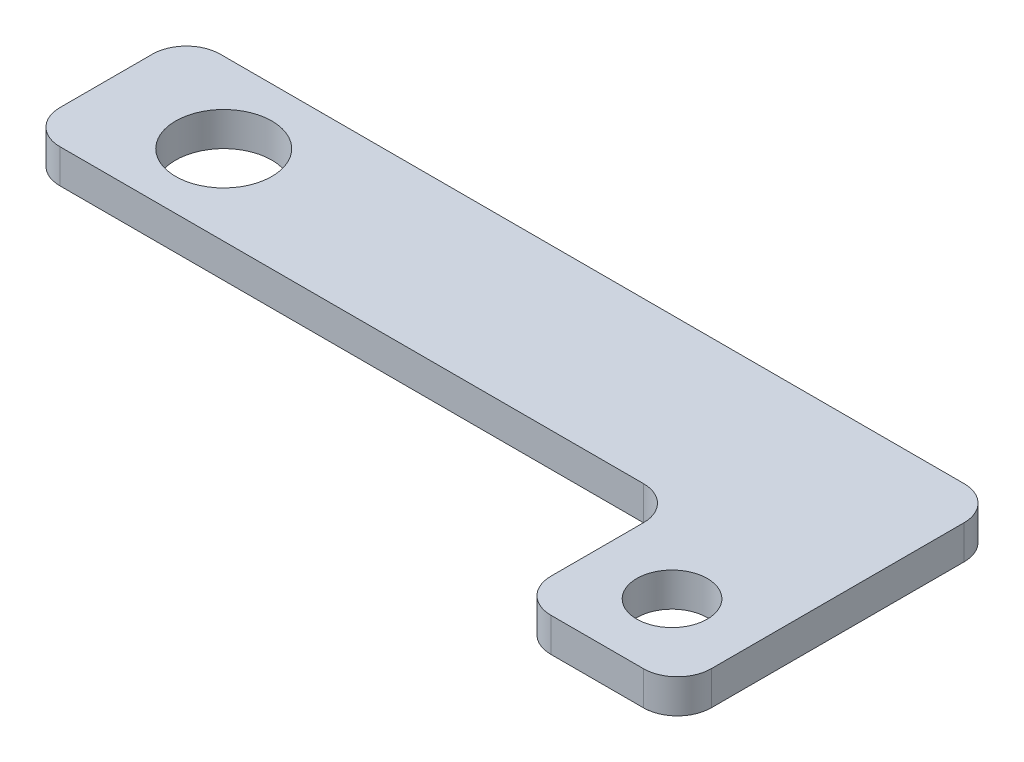
SolidWorks part; units mm, degrees
material "3003-H14"
ref_plane "X-Y Datum" through (0, 0, 0) normal (0, 0, 1) x (1, 0, 0)
ref_plane "X-Z Datum" through (0, 0, 0) normal (0, 1, 0) x (1, 0, 0)
ref_plane "Y-Z Datum" through (0, 0, 0) normal (1, 0, 0) x (0, 0, -1)
sketch "Sketch1" plane through (0, 0, 0) normal (0, 1, 0) x (1, 0, 0)
  line L0 (56, -44.0812) -> (71, -44.0812) construction
  line L1 (6.05, -36.0812) -> (6.05, -21.0812) construction
  line L2 (6.05, -36.0812) -> (56, -36.0812)
  line L3 (56, -36.0812) -> (56, -44.0812)
  line L4 (6.05, -21.0812) -> (71, -21.0812)
  line L5 (71, -21.0812) -> (71, -44.0812)
  line L6 (56, -44.0812) -> (56, -51.0812)
  line L7 (56, -51.0812) -> (71, -51.0812)
  line L8 (71, -51.0812) -> (71, -44.0812)
  line L9 (6.05, -21.0812) -> (-4.95, -21.0812)
  line L10 (-4.95, -21.0812) -> (-4.95, -36.0812)
  line L11 (-4.95, -36.0812) -> (6.05, -36.0812)
  point P0 (63.5, -44.0812)
  point P1 (6.05, -28.5812)
  point P3 (6.05, -28.5812)
  point P7 (63.5, -44.0812)
  point P10 (6.05, -28.5812)
  point P17 (0, 0)
  point P18 (6.05, -28.5812)
  dimension "D1" = 15
  dimension "D2" = 15
  dimension "D3" = 11
  dimension "D4" = 7
extrude "Boss-Extrude1" add sketch "Sketch1" against normal blind 3.175
hole_wizard "M8 Clearance Hole1" positions "Sketch4" profile "Sketch3" hole size "M8" standard "ANSI Metric" end condition through all
sketch "Sketch4" plane through (0, -3.175, 0) normal (0, -1, 0) x (-1, 0, 0)
  point P0 (-6.05, -28.5812)
sketch "Sketch3" plane through (6.05, -3.175, 28.5812) normal (1, 0, 0) x (0, 0, -1)
  line L0 (0, 0) -> (0, 3.175)
  line L1 (0, 3.175) -> (4.5, 3.175)
  line L2 (4.5, 3.175) -> (4.5, 0)
  line L5 (4.5, 0) -> (0, 0)
  line L11 (0, -6.35) -> (0, 107.95) construction
  dimension "Thru Hole Dia." = 9
  dimension "Thru Hole Depth" = 3.175
hole_wizard "M6 Clearance Hole1" positions "Sketch7" profile "Sketch6" hole size "M6" standard "ANSI Metric" end condition through all
sketch "Sketch7" plane through (0, -3.175, 0) normal (0, -1, 0) x (-1, 0, 0)
  point P0 (-63.5, -44.0812)
sketch "Sketch6" plane through (63.5, -3.175, 44.0812) normal (1, 0, 0) x (0, 0, -1)
  line L0 (0, 0) -> (0, 3.175)
  line L1 (0, 3.175) -> (3.3, 3.175)
  line L2 (3.3, 3.175) -> (3.3, 0)
  line L5 (3.3, 0) -> (0, 0)
  line L11 (0, -6.35) -> (0, 107.95) construction
  dimension "Thru Hole Dia." = 6.6
  dimension "Thru Hole Depth" = 3.175
fillet "Fillet1" radius 3.175 6 edges at (71, -1.5875, 21.0812) (-4.95, -1.5875, 21.0812) (-4.95, -1.5875, 36.0812) (56, -1.5875, 36.0812) (71, -1.5875, 51.0812) (56, -1.5875, 51.0812)
